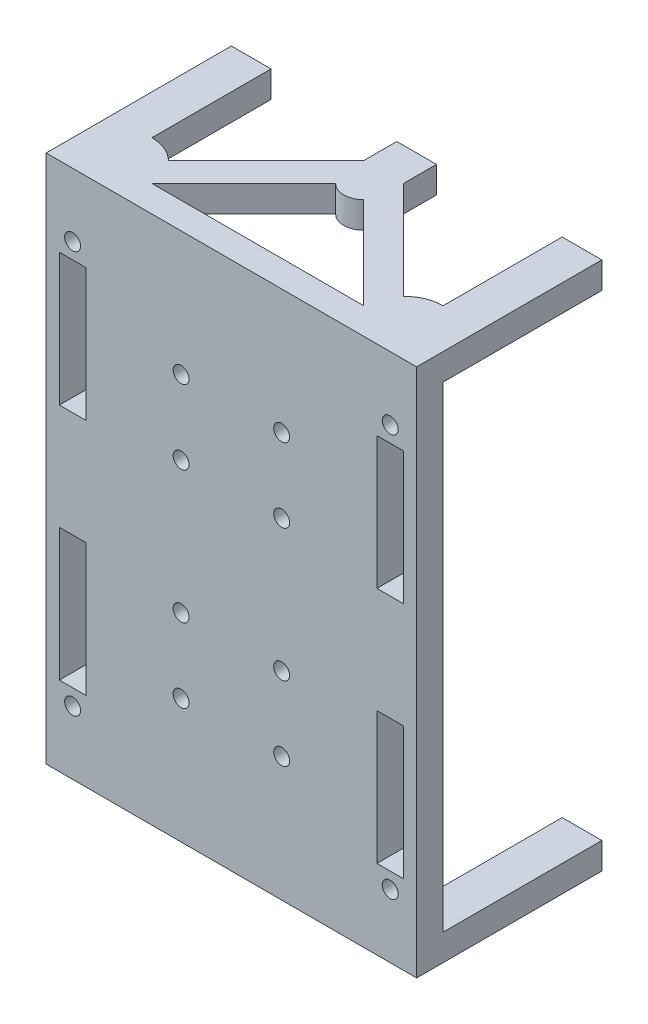
SolidWorks part; units mm, degrees
ref_plane "Front Plane" through (0, 0, 0) normal (0, 0, 1) x (1, 0, 0)
ref_plane "Top Plane" through (0, 0, 0) normal (0, 1, 0) x (1, 0, 0)
ref_plane "Right Plane" through (0, 0, 0) normal (1, 0, 0) x (0, 0, -1)
sketch "Sketch1" plane through (0, 0, 0) normal (0, 0, 1) x (1, 0, 0)
  line L1 (-35, -50) -> (35, -50)
  line L2 (-35, -50) -> (-35, 50)
  line L3 (-35, 50) -> (35, 50)
  line L4 (35, -50) -> (35, 50)
  line L5 (-35, -50) -> (35, 50) construction
  line L6 (-35, 50) -> (35, -50) construction
  point P0 (0, 0)
  dimension "D1" = 70
  dimension "D2" = 100
extrude "Boss-Extrude1" add sketch "Sketch1" along normal mid plane 5
sketch "Sketch2" plane through (0, 0, -2.5) normal (0, 0, -1) x (-1, 0, 0)
  line L0 (25, 26) -> (35, 50)
  line L1 (35, 50) -> (25, 50)
  line L2 (35, 50) -> (35, 26)
  line L3 (35, 26) -> (25, 26)
  line L4 (25, 50) -> (25, 26)
  line L5 (0, 50) -> (0, -50) construction
  line L6 (-35, 50) -> (35, 50) construction
  line L7 (35, -50) -> (-35, -50) construction
  line L8 (-35, 0) -> (35, 0) construction
  line L9 (-35, -50) -> (-35, 50) construction
  line L10 (35, 50) -> (35, -50) construction
  circle A0 centre (30, 38) radius 1.5
  circle A1 centre (-30, 38) radius 1.5
  circle A2 centre (30, -38) radius 1.5
  circle A3 centre (-30, -38) radius 1.5
  dimension "D3" = 3
  dimension "D1" = 24
  dimension "D2" = 10
extrude "Cut-Extrude1" cut sketch "Sketch2" against normal blind 10 contours A0 | A2 | A3 | A1
sketch "Sketch3" plane through (0, 50, 0) normal (0, 1, 0) x (1, 0, 0)
  line L0 (-35, 2.5) -> (-35, 32.5)
  line L1 (0, 2.5) -> (0, 18.75) construction
  line L2 (35, 2.5) -> (-35, 2.5) construction
  line L3 (-35, 32.5) -> (-27.5, 32.5)
  line L4 (-27.5, 32.5) -> (-27.5, 10)
  line L5 (-22.1967, 7.8033) -> (-3.75, 26.25)
  line L6 (-35, 2.5) -> (-20, 2.5)
  line L7 (-20, 2.5) -> (-2.6517, 19.8483)
  line L8 (20, 2.5) -> (35, 2.5)
  line L10 (-3.75, 32.5) -> (3.75, 32.5)
  line L11 (-3.75, 26.25) -> (-3.75, 32.5)
  line L14 (3.75, 26.25) -> (3.75, 32.5)
  line L15 (2.6517, 19.8483) -> (20, 2.5)
  line L16 (22.1967, 7.8033) -> (3.75, 26.25)
  line L17 (35, 32.5) -> (27.5, 32.5)
  line L18 (27.5, 32.5) -> (27.5, 10)
  line L19 (35, 2.5) -> (35, 32.5)
  line L20 (0, 22.5) -> (0, 51.9526) construction
  arc A1 (-22.1967, 7.8033) -> (-27.5, 10) centre (-27.5, 2.5) ccw
  arc A2 (22.1967, 7.8033) -> (27.5, 10) centre (27.5, 2.5) cw
  arc A3 (-2.6517, 19.8483) -> (2.6517, 19.8483) centre (0, 22.5) ccw
  point P22 (0, 32.5)
  dimension "D5" = 7.5
  dimension "D1" = 30
  dimension "D2" = 7.5
extrude "Boss-Extrude2" add sketch "Sketch3" against normal blind 5
mirror "Mirror1" about plane through (0, 0, 0) normal (0, 1, 0) of "Boss-Extrude2"
sketch "Sketch4" plane through (0, 0, -2.5) normal (0, 0, -1) x (-1, 0, 0)
  line L0 (-35, 0) -> (35, 0) construction
  line L1 (-35, -45) -> (-35, 45) construction
  line L2 (35, 45) -> (35, -45) construction
  line L3 (-11.5, 8) -> (-11.5, 12.5)
  line L4 (32.5, 35) -> (27.5, 35)
  line L5 (-11.5, 37) -> (11.5, 37)
  line L6 (-11.5, 37) -> (-11.5, 8)
  line L7 (-11.5, 8) -> (11.5, 8)
  line L8 (11.5, 37) -> (11.5, 8)
  line L9 (-11.5, 37) -> (11.5, 8) construction
  line L10 (-11.5, 8) -> (11.5, 37) construction
  line L11 (27.5, 10) -> (27.5, 35)
  line L12 (0, 22.5) -> (0, 45) construction
  line L13 (-32.5, 10) -> (-27.5, 10)
  line L14 (-32.5, 10) -> (-32.5, 35)
  line L15 (-32.5, 35) -> (-27.5, 35)
  line L16 (-27.5, 10) -> (-27.5, 35)
  line L17 (-32.5, 10) -> (-27.5, 35) construction
  line L18 (-32.5, 35) -> (-27.5, 10) construction
  line L19 (-3.75, 45) -> (3.75, 45) construction
  line L20 (0, 45) -> (0, 0) construction
  line L21 (-11.5, 12.5) -> (-9.5, 12.5)
  line L22 (-9.5, 12.5) -> (-9.5, 26.5)
  line L23 (32.5, 10) -> (27.5, 10)
  line L24 (32.5, 10) -> (32.5, 35)
  line L25 (32.5, -10) -> (32.5, -35)
  line L26 (32.5, -10) -> (27.5, -10)
  line L27 (27.5, -10) -> (27.5, -35)
  line L28 (32.5, -35) -> (27.5, -35)
  line L29 (-32.5, -35) -> (-27.5, -35)
  line L30 (-27.5, -10) -> (-27.5, -35)
  line L31 (-32.5, -10) -> (-27.5, -10)
  line L32 (-32.5, -10) -> (-32.5, -35)
  circle A0 centre (-9.5, 12.5) radius 1.5
  circle A1 centre (-9.5, 26.5) radius 1.5
  circle A2 centre (9.5, 12.5) radius 1.5
  circle A3 centre (9.5, 26.5) radius 1.5
  circle A4 centre (9.5, -12.5) radius 1.5
  circle A5 centre (9.5, -26.5) radius 1.5
  circle A6 centre (-9.5, -26.5) radius 1.5
  circle A7 centre (-9.5, -12.5) radius 1.5
  dimension "D8" = 3
  dimension "D10" = 3
  dimension "D1" = 22.5
  dimension "D2" = 23
  dimension "D3" = 29
  dimension "D4" = 5
  dimension "D5" = 25
  dimension "D6" = 4.5
  dimension "D7" = 2
  dimension "D9" = 14
extrude "Cut-Extrude2" cut sketch "Sketch4" against normal blind 5 contours L31 L32 L29 L30 | A6 | A7 | A4 | A5 | L27 L28 L25 L26 | L11 L4 L24 L23 | A2 | A3 | A1 | A0 | L16 L15 L14 L13 region at (30, -22.5, -2.5)
sketch "Sketch7" plane through (0, 0, -32.5) normal (0, 0, -1) x (-1, 0, 0)
  line L0 (-3.75, 50) -> (3.75, 45)
  line L1 (-35, 50) -> (-27.5, 45)
  line L2 (35, 50) -> (27.5, 45)
  line L3 (27.5, 45) -> (27.5, 50) construction
  line L4 (27.5, 45) -> (35, 45) construction
  circle A0 centre (0, 47.5) radius 1.5
  circle A1 centre (-31.25, 47.5) radius 1.5
  circle A2 centre (31.25, 47.5) radius 1.5
  dimension "D1" = 3
  dimension "D2" = 3
  dimension "D3" = 3
extrude "Cut-Extrude3" cut sketch "Sketch7" against normal blind 5 contours A1 | A0 | A2
mirror "Mirror2" about plane through (0, 0, 0) normal (0, 1, 0) of "Cut-Extrude3"
